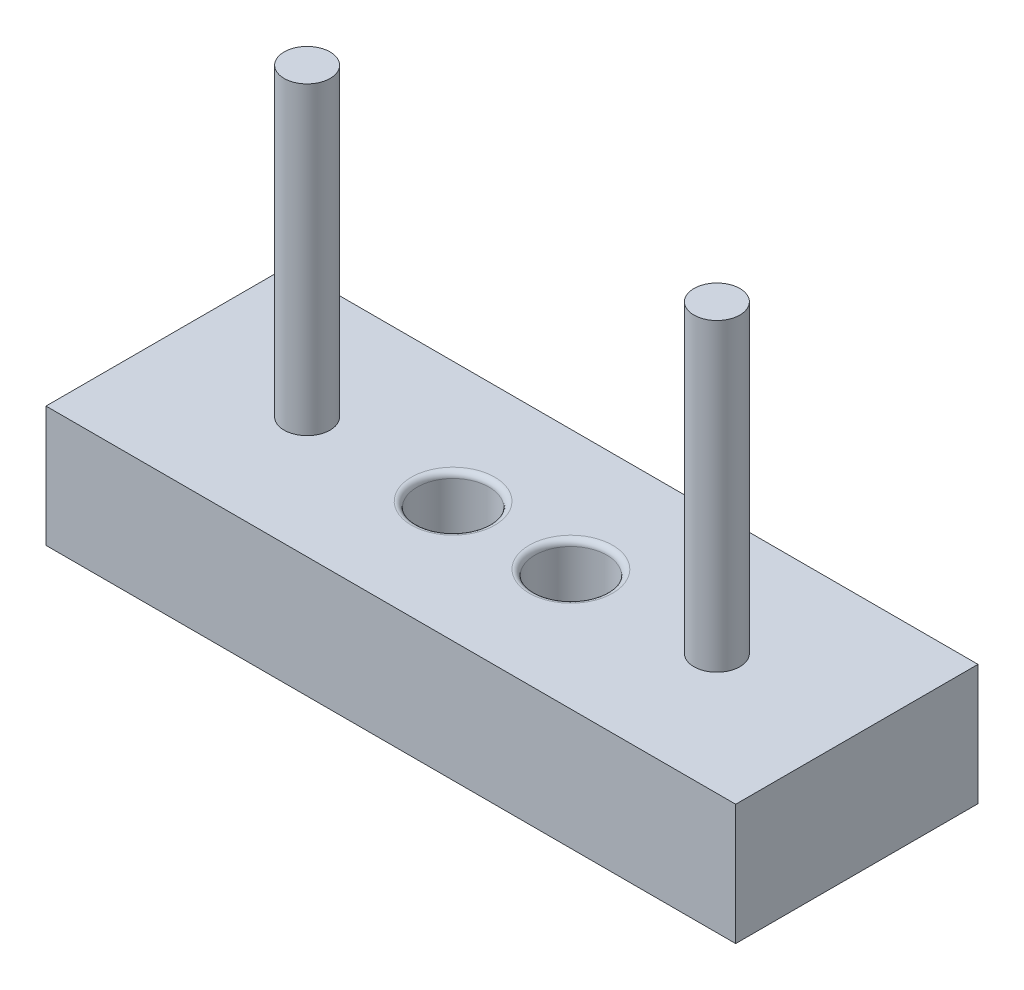
SolidWorks part; units mm, degrees
ref_plane "Front Plane" through (0, 0, 0) normal (0, 0, 1) x (1, 0, 0)
ref_plane "Top Plane" through (0, 0, 0) normal (0, 1, 0) x (1, 0, 0)
ref_plane "Right Plane" through (0, 0, 0) normal (1, 0, 0) x (0, 0, -1)
sketch "Sketch1" plane through (0, 0, 0) normal (0, 1, 0) x (1, 0, 0)
  line L1 (-43.189, 20.5655) -> (76.811, 20.5655)
  line L2 (-43.189, 20.5655) -> (-43.189, -21.5945)
  line L3 (-43.189, -21.5945) -> (76.811, -21.5945)
  line L4 (76.811, 20.5655) -> (76.811, -21.5945)
  dimension "D1" = 42.16
  dimension "D2" = 120
extrude "Boss-Extrude1" add sketch "Sketch1" along normal blind 21
sketch "Sketch2" plane through (0, 21, 0) normal (0, 1, 0) x (1, 0, 0)
  line L0 (-43.189, -0.5145) -> (76.811, -0.5145) construction
  line L1 (16.811, -21.5945) -> (16.811, 20.5655) construction
  line L2 (27.061, -21.5945) -> (27.061, 20.5655)
  line L3 (6.561, -21.5945) -> (6.561, 20.5655)
  line L4 (-43.189, 20.5655) -> (-43.189, -21.5945)
  line L5 (-43.189, -21.5945) -> (76.811, -21.5945)
  line L6 (76.811, -21.5945) -> (76.811, 20.5655)
  line L7 (76.811, 20.5655) -> (-43.189, 20.5655)
  line L8 (-43.189, 20.5655) -> (-43.189, -21.5945)
  line L9 (-43.189, -21.5945) -> (76.811, -21.5945)
  line L10 (76.811, -21.5945) -> (76.811, 20.5655)
  line L11 (76.811, 20.5655) -> (-43.189, 20.5655)
  circle A0 centre (27.061, -0.5145) radius 6.25
  circle A1 centre (6.561, -0.5145) radius 6.25
  dimension "D1" = 0
  dimension "D2" = 21.08
  dimension "D3" = 60
  dimension "D4" = 10.25
  dimension "D5" = 10.25
extrude "Cut-Extrude1" cut sketch "Sketch2" against normal blind 14 contours L2 A0 | L2 A0 | L3 A1 | L3 A1 region at (24.4084, 21, 0.5145) region at (29.7136, 21, 0.5145) region at (3.9084, 21, 0.5145) region at (9.2136, 21, 0.5145)
sketch "Sketch3" plane through (0, 7, 0) normal (0, 1, 0) x (1, 0, 0)
  circle A4 centre (27.061, -0.5145) radius 3.25
  circle A5 centre (6.561, -0.5145) radius 3.25
extrude "Cut-Extrude2" cut sketch "Sketch3" against normal through all
fillet "Fillet1" radius 1 2 edges at (6.561, 21, 6.7645) (27.061, 21, 6.7645)
fillet "Fillet2" radius 0.5 2 edges at (6.561, 0, 3.7645) (27.061, 0, 3.7645)
sketch "Sketch4" plane through (0, 21, 0) normal (0, 1, 0) x (1, 0, 0)
  line L0 (6.561, -0.5145) -> (27.061, -0.5145) construction
  line L1 (76.811, 20.5655) -> (-43.189, 20.5655) construction
  line L2 (-43.189, -21.5945) -> (76.811, -21.5945) construction
  line L3 (52.461, -21.5945) -> (52.461, 20.5655)
  line L6 (-18.839, -21.5945) -> (-18.839, 20.5655)
  circle A0 centre (52.461, -0.5145) radius 4
  circle A1 centre (-18.839, -0.5145) radius 4
  point P12 (16.811, -0.5145)
  dimension "D4" = 8
  dimension "D1" = 71.3
  dimension "D2" = 35.65
extrude "Boss-Extrude2" add sketch "Sketch4" along normal blind 53 contours L3 A0 | L3 A0 | L6 A1 | L6 A1 region at (50.7634, 21, 0.5145) region at (54.1587, 21, 0.5145) region at (-20.5366, 21, 0.5145) region at (-17.1413, 21, 0.5145)
sketch "Sketch5" plane through (0, 21, 0) normal (0, 1, 0) x (1, 0, 0)
  circle A1 centre (52.461, -0.5145) radius 4 construction
  circle A3 centre (52.461, -0.5145) radius 4
curve "Helix/Spiral1" [suppressed] pitch 0.75 height 54 turns 72
sketch "Sketch6" plane through (0, 74, 0) normal (0, 1, 0) x (1, 0, 0)
  circle A1 centre (52.461, -0.5145) radius 4
  circle A2 centre (52.461, -0.5145) radius 4
  dimension "D1" = 0
ref_plane "Plane1" through (0, 0, 0.5145) normal (0, 0, 1) x (1, 0, 0)
sketch "Sketch18" plane through (0, 0, 0.5145) normal (0, 0, 1) x (1, 0, 0)
  line L3 (-43.189, 21) -> (76.811, 21) construction
  line L4 (59.811, 21) -> (60.561, 21)
  line L7 (59.811, 21) -> (60.561, 20.5)
  line L8 (60.561, 20.5) -> (60.561, 21)
  dimension "D1" = 0.75
  dimension "D2" = 0.5
sweep "Cut-Sweep3" [suppressed] cut profiles "Sketch18" path "Helix/Spiral1"
ref_plane "Plane2" through (16.811, 0, 0) normal (-1, 0, 0) x (0, 0, -1)
mirror "Mirror1" [suppressed] about plane through (16.811, 0, 0) normal (-1, 0, 0)
